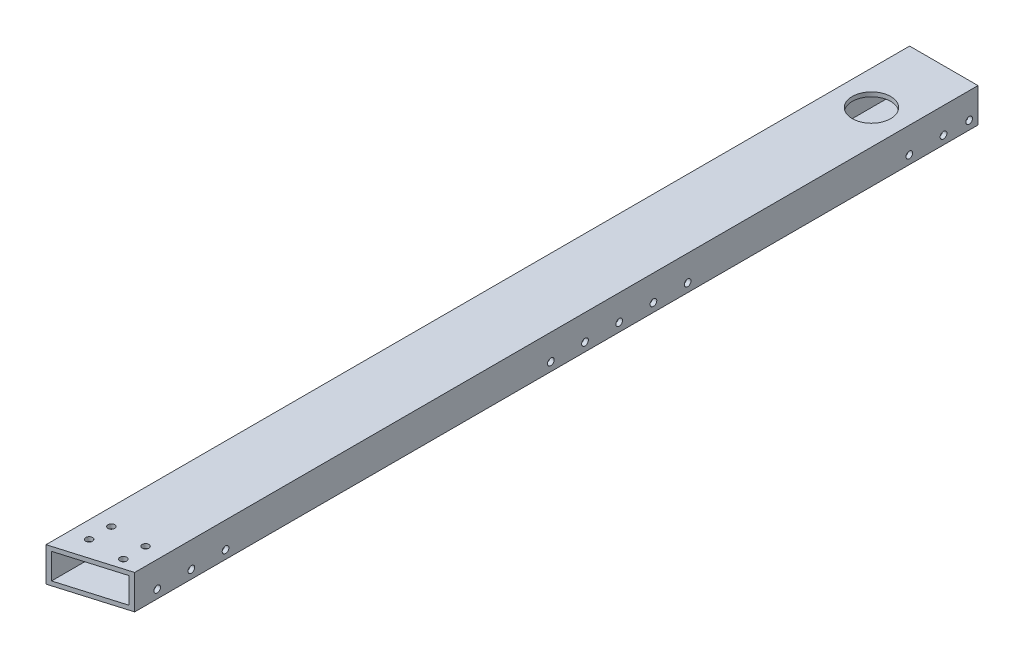
SolidWorks part; units mm, degrees
ref_plane "Front Plane" through (0, 0, 0) normal (0, 0, 1) x (1, 0, 0)
ref_plane "Top Plane" through (0, 0, 0) normal (0, 1, 0) x (1, 0, 0)
ref_plane "Right Plane" through (0, 0, 0) normal (1, 0, 0) x (0, 0, -1)
sketch "Sketch1" plane through (0, 0, 0) normal (0, 0, 1) x (1, 0, 0)
  line L0 (-22.225, 9.525) -> (22.225, 9.525)
  line L2 (-25.4, 12.7) -> (25.4, 12.7)
  line L3 (-25.4, 12.7) -> (-25.4, -12.7)
  line L4 (-25.4, -12.7) -> (25.4, -12.7)
  line L5 (25.4, 12.7) -> (25.4, -12.7)
  line L10 (22.225, 9.525) -> (22.225, -9.525)
  line L11 (-22.225, -9.525) -> (22.225, -9.525)
  line L12 (-22.225, 9.525) -> (-22.225, -9.525)
  point P12 (0, 12.7)
  point P14 (25.4, 0)
  dimension "Wall Thickness" = 3.175
  dimension "Outside Width" = 50.8
  dimension "Outside Height" = 25.4
  dimension "Inside Height" = 19.05
  dimension "Inside Width" = 44.45
sketch "Sketch2" plane through (0, 0, 0) normal (1, 0, 0) x (0, 0, -1)
  line L0 (320.675, 0) -> (-320.675, 0)
  point P4 (0, 0)
  point P7 (-320.675, 0)
  point P10 (320.675, 0)
  dimension "Length" = 641.35
sketch "Sketch3" plane through (0, 0, 0) normal (0, 0, 1) x (1, 0, 0)
  line L21 (25.4, 12.7) -> (-25.4, 12.7)
  line L22 (25.4, -12.7) -> (25.4, 12.7)
  line L23 (-25.4, -12.7) -> (25.4, -12.7)
  line L24 (-25.4, 12.7) -> (-25.4, -12.7)
  line L25 (25.4, 12.7) -> (-25.4, 12.7)
  line L26 (25.4, -12.7) -> (25.4, 12.7)
  line L27 (-25.4, -12.7) -> (25.4, -12.7)
  line L28 (-25.4, 12.7) -> (-25.4, -12.7)
  line L29 (22.225, 9.525) -> (-22.225, 9.525)
  line L30 (22.225, -9.525) -> (22.225, 9.525)
  line L31 (-22.225, -9.525) -> (22.225, -9.525)
  line L32 (-22.225, 9.525) -> (-22.225, -9.525)
  line L33 (22.225, 9.525) -> (-22.225, 9.525)
  line L34 (22.225, -9.525) -> (22.225, 9.525)
  line L35 (-22.225, -9.525) -> (22.225, -9.525)
  line L36 (-22.225, 9.525) -> (-22.225, -9.525)
  dimension "D1" = 0
  dimension "D2" = 0
extrude "Boss-Extrude1" add sketch "Sketch3" along normal up to vertex (320.675 mm away) and the other way up to vertex (320.675 mm away) up to point (0, 0, 320.675) other way up to point (0, 0, -320.675)
sketch "Drawing Reference" plane through (0, 0, 0) normal (1, 0, 0) x (0, 0, -1)
  line L0 (-320.675, 0) -> (320.675, 0) construction
  line L1 (0, -12.7) -> (0, 12.7) construction
  line L2 (-320.675, -12.7) -> (320.675, -12.7) construction
  line L5 (-320.675, 12.7) -> (320.675, 12.7) construction
  point P7 (-284.099, 0)
  point P8 (284.099, 0)
  dimension "D1" = 36.576
sketch "Sketch4" plane through (0, 12.7, 0) normal (0, 1, 0) x (1, 0, 0)
  line L0 (-25.4, -320.675) -> (25.4, -305.6274)
  line L1 (25.4, -320.675) -> (25.4, 320.675) construction
  line L2 (25.4, -320.675) -> (-25.4, -320.675)
  dimension "D1" = 16.5
extrude "Cut-Extrude1" cut sketch "Sketch4" against normal through all and the other way through all flip side to cut
sketch "Sketch8" plane through (0, 12.7, 0) normal (0, 1, 0) x (1, 0, 0)
  line L0 (0, 320.675) -> (0, 266.954) construction
  line L1 (25.4, 320.675) -> (-25.4, 320.675) construction
  circle A0 centre (0, 266.954) radius 14.2875
  dimension "D1" = 53.721
extrude "Cut-Extrude2" cut sketch "Sketch8" against normal through all
sketch "Sketch9" plane through (0, 12.7, 0) normal (0, 1, 0) x (1, 0, 0)
  line L0 (-12.7762, -284.753) -> (12.6238, -284.753) construction
  line L1 (12.6238, -284.753) -> (12.6238, -301.263) construction
  line L2 (12.6238, -301.263) -> (-12.7762, -301.263) construction
  line L3 (-12.7762, -301.263) -> (-12.7762, -284.753) construction
hole_wizard "#10 Clearance Hole1" positions "Sketch10" profile "Sketch11" hole size "#10" standard "ANSI Inch"
sketch "Sketch10" plane through (0, 12.7, 0) normal (0, 1, 0) x (1, 0, 0)
  point P0 (-12.7762, -284.753)
  point P3 (12.6238, -284.753)
  point P6 (12.6238, -301.263)
  point P9 (-12.7762, -301.263)
sketch "Sketch11" plane through (-12.7762, 12.7, 284.753) normal (1, 0, 0) x (0, 0, 1)
  line L0 (0, 0) -> (0, 6.5757)
  line L1 (0, 6.5757) -> (2.4892, 5.08)
  line L2 (2.4892, 5.08) -> (2.4892, 0)
  line L5 (2.4892, 0) -> (0, 0)
  line L10 (0, 6.5757) -> (-2.4892, 5.08) construction
  line L11 (0, -6.35) -> (0, 107.95) construction
  dimension "Hole Dia." = 4.9784
  dimension "Hole Depth" = 5.08
  dimension "Drill Angle" = 118
hole_wizard "#10 Clearance Hole2" positions "Sketch12" profile "Sketch13" hole size "#10" standard "ANSI Inch" end condition through all
sketch "Sketch12" plane through (25.4, 0, 0) normal (1, 0, 0) x (0, 0, -1)
  point P9 (3.429, -6.35)
  point P12 (28.829, -6.35)
  point P15 (54.229, -6.35)
  point P18 (79.629, -6.35)
  point P21 (105.029, -6.35)
  point P24 (-288.925, -6.35)
  point P27 (-263.525, -6.35)
  point P30 (-238.1261, -6.3882)
sketch "Sketch13" plane through (25.4, -6.35, -3.429) normal (0, 1, 0) x (0, 0, -1)
  line L0 (0, 0) -> (0, 50.8)
  line L1 (0, 50.8) -> (2.4892, 50.8)
  line L2 (2.4892, 50.8) -> (2.4892, 0)
  line L5 (2.4892, 0) -> (0, 0)
  line L11 (0, -6.35) -> (0, 107.95) construction
  dimension "Thru Hole Dia." = 4.9784
  dimension "Thru Hole Depth" = 50.8
hole_wizard "#10 Clearance Hole3" positions "Sketch14" profile "Sketch15" hole size "#10" standard "ANSI Inch"
sketch "Sketch14" plane through (25.4, 0, 0) normal (1, 0, 0) x (0, 0, -1)
  point P0 (269.6733, -6.3882)
  point P3 (295.0733, -6.3882)
  point P6 (314.1233, -6.3882)
sketch "Sketch15" plane through (25.4, -6.3882, -269.6733) normal (0, 1, 0) x (0, 0, -1)
  line L0 (0, 0) -> (0, 4.7977)
  line L1 (0, 4.7977) -> (2.4892, 3.302)
  line L2 (2.4892, 3.302) -> (2.4892, 0)
  line L5 (2.4892, 0) -> (0, 0)
  line L10 (0, 4.7977) -> (-2.4892, 3.302) construction
  line L11 (0, -6.35) -> (0, 107.95) construction
  dimension "Hole Dia." = 4.9784
  dimension "Hole Depth" = 3.302
  dimension "Drill Angle" = 118
equation "\"D1@Drawing Reference\"=\"Outside Width@Sketch1\" * 0.72"
